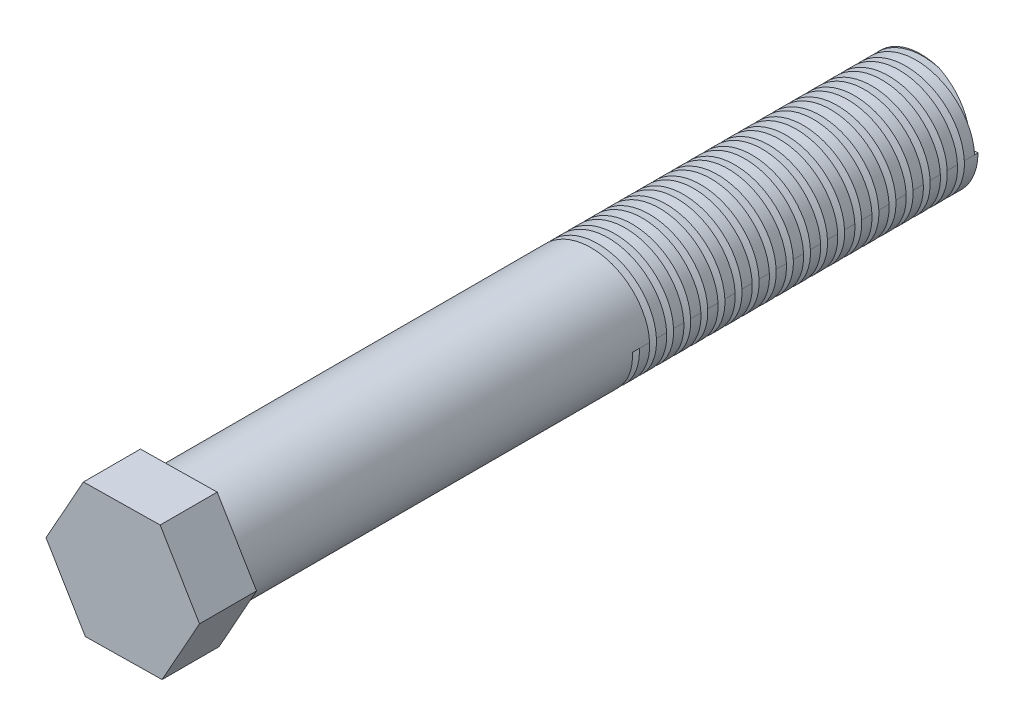
SolidWorks part; units mm, degrees
material "AISI 4140 Steel, quenched & tempered"
ref_plane "Front Plane" through (0, 0, 0) normal (1, 0, 0) x (0, 1, 0)
ref_plane "Top Plane" through (0, 0, 0) normal (0, 0, 1) x (0, 1, 0)
ref_plane "Right Plane" through (0, 0, 0) normal (0, 1, 0) x (-1, 0, 0)
sketch "Sketch1" plane through (0, 0, 0) normal (0, 0, 1) x (0, 1, 0)
  circle A0 centre (0, 0) radius 5
  dimension "D1" = 10
extrude "Boss-Extrude1" add sketch "Sketch1" against normal blind 65
sketch "Sketch2" plane through (0, 0, 0) normal (0, 0, 1) x (1, 0, 0)
  line L1 (6.7305, 0.0965) -> (3.2816, 5.877)
  line L2 (3.2816, 5.877) -> (-3.4489, 5.7805)
  line L3 (-3.4489, 5.7805) -> (-6.7305, -0.0965)
  line L4 (-6.7305, -0.0965) -> (-3.2816, -5.877)
  line L5 (-3.2816, -5.877) -> (3.4489, -5.7805)
  line L6 (3.4489, -5.7805) -> (6.7305, 0.0965)
  circle A0 centre (0, 0) radius 5.8294 construction
extrude "Boss-Extrude2" add sketch "Sketch2" along normal blind 5
thread "Thread1" pitch 10 method cut profile "Thread Profile1" start angle 0, offset 0, length 30, pitch 1.5, diameter 10
ref_plane "Plane1" through (5, 0, -65) normal (0, -1, 0) x (1, 0, 0)
sketch "Thread Profile1" plane through (5, 0, -65) normal (0, -1, 0) x (1, 0, 0)
  line L0 (0, 0.5899) -> (0, -0.6149) construction
  line L1 (-0.6384, 0) -> (0.768, 0) construction
  line L2 (0, 0.3) -> (0, -0.3)
  line L3 (0, -0.3) -> (-0.6, -0.075)
  line L4 (-0.6, -0.075) -> (-0.6, 0.075)
  line L5 (-0.6, 0.075) -> (0, 0.3)
  point P7 (-0.6, 0)
  point P10 (0, 0)
  dimension "D1" = 0.6
  dimension "D2" = 0.6
  dimension "D3" = 0.15
